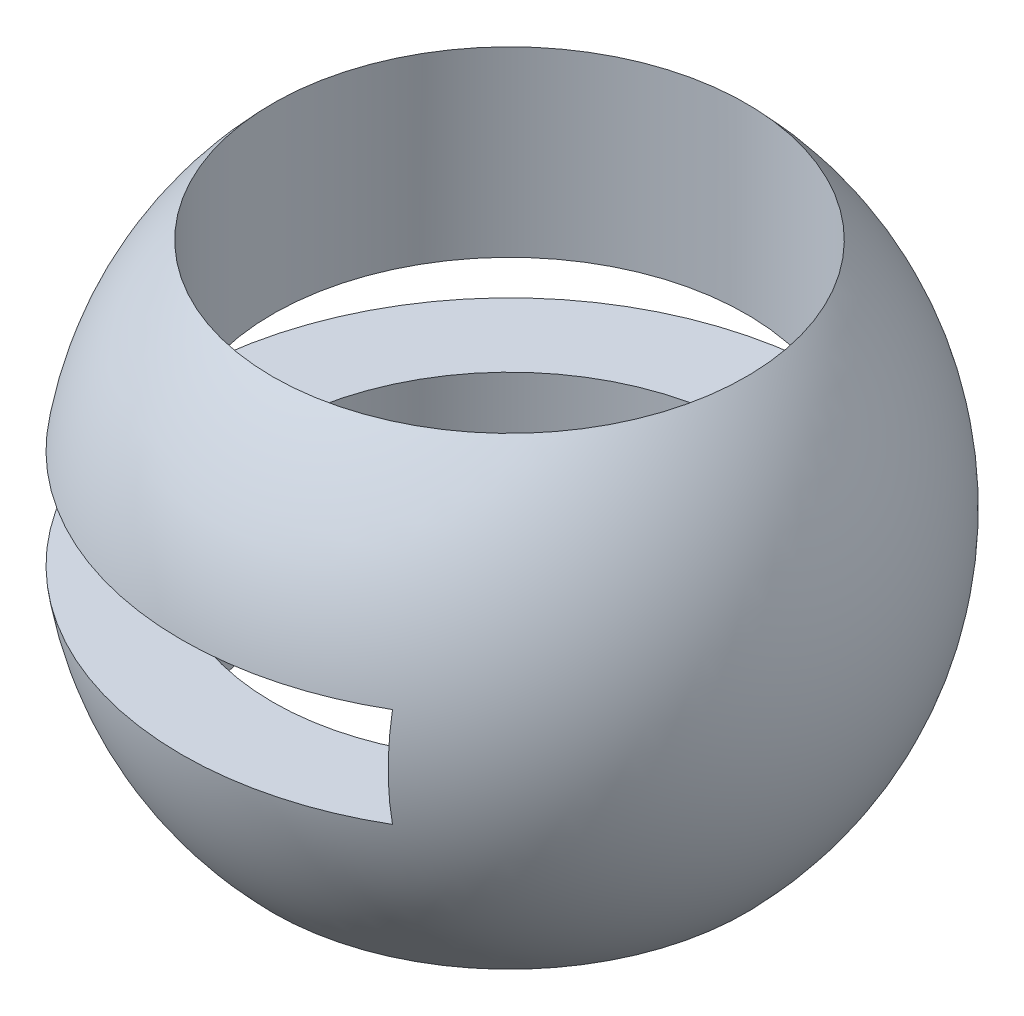
SolidWorks part; units mm, degrees
ref_plane "Alzado" through (0, 0, 0) normal (0, 0, 1) x (1, 0, 0)
ref_plane "Planta" through (0, 0, 0) normal (0, 1, 0) x (1, 0, 0)
ref_plane "Vista lateral" through (0, 0, 0) normal (1, 0, 0) x (0, 0, -1)
sketch "Croquis1" plane through (0, 0, 0) normal (0, 0, 1) x (1, 0, 0)
  line L0 (0, 27.4521) -> (0, -26845.4162) construction
  line L4 (0, 20) -> (0, -20)
  arc A1 (0, -20) -> (0, 20) centre (0, 0) ccw
  dimension "D1" = 40
revolve "Revolución1" add sketch "Croquis1" angle 360 about L0
sketch "Croquis3" plane through (0, 0, 0) normal (0, 0, 1) x (1, 0, 0)
  line L0 (0, 20) -> (0, -49980) construction
  line L1 (0, 20) -> (-20, 20)
  line L2 (0, 20) -> (0, 14)
  line L3 (0, 14) -> (-20, 14)
  line L4 (-20, 20) -> (-20, 14)
  line L5 (0, 0) -> (50000, 0) construction
  circle A0 centre (0, 0) radius 20 construction
  dimension "D1" = 6
  dimension "D2" = 20
  dimension "D3" = 14
revolve "Cortar-Revolución1" cut sketch "Croquis3" angle 360 about L0
sketch "Croquis4" plane through (0, 0, 0) normal (0, 0, 1) x (1, 0, 0)
  line L0 (0, 0) -> (0, -20) construction
  line L1 (0, 0) -> (20, 0) construction
  line L3 (0, -20) -> (20, -20)
  line L4 (0, -20) -> (0, -14)
  line L5 (0, -14) -> (20, -14)
  line L6 (20, -20) -> (20, -14)
  arc A2 (-14.2829, 14) -> (14.2829, 14) centre (0, 0) ccw construction
  dimension "D1" = 6
  dimension "D2" = 20
revolve "Cortar-Revolución2" cut sketch "Croquis4" angle 360 about L0
sketch "Croquis7" plane through (0, 14, 0) normal (0, 1, 0) x (1, 0, 0)
  circle A0 centre (0, 0) radius 14.2829
  dimension "D1" = 28.5657
sketch "Croquis8" plane through (0, 14, 0) normal (0, 1, 0) x (1, 0, 0)
  circle A0 centre (0, 0) radius 14.2829
  dimension "D1" = 28.5657
extrude "Cortar-Extruir2" cut sketch "Croquis8" against normal through all
sketch "Croquis9" plane through (0, 0, 0) normal (0, 0, 1) x (1, 0, 0)
  line L0 (0, 0) -> (0, 50000) construction
  line L1 (14.2829, 14) -> (-14.2829, 14) construction
  line L2 (0, 0) -> (50000, 0) construction
  line L6 (-20, -3) -> (10, -3)
  line L7 (10, 0) -> (10, -3)
  line L10 (-20, 3) -> (10, 3)
  line L11 (10, 0) -> (10, 3)
  line L12 (-20, 3) -> (-20, -3)
  arc A0 (14.2829, -14) -> (14.2829, 14) centre (0, 0) ccw construction
  point P5 (0, 14)
  point P11 (20, 0)
  dimension "D1" = 6
  dimension "D2" = 30
  dimension "D3" = 3
extrude "Cortar-Extruir3" cut sketch "Croquis9" against normal blind 34 and the other way blind 34
scale "Escala1" bodies to scale 107 scale about origin uniform scaling yes scale factor 5
